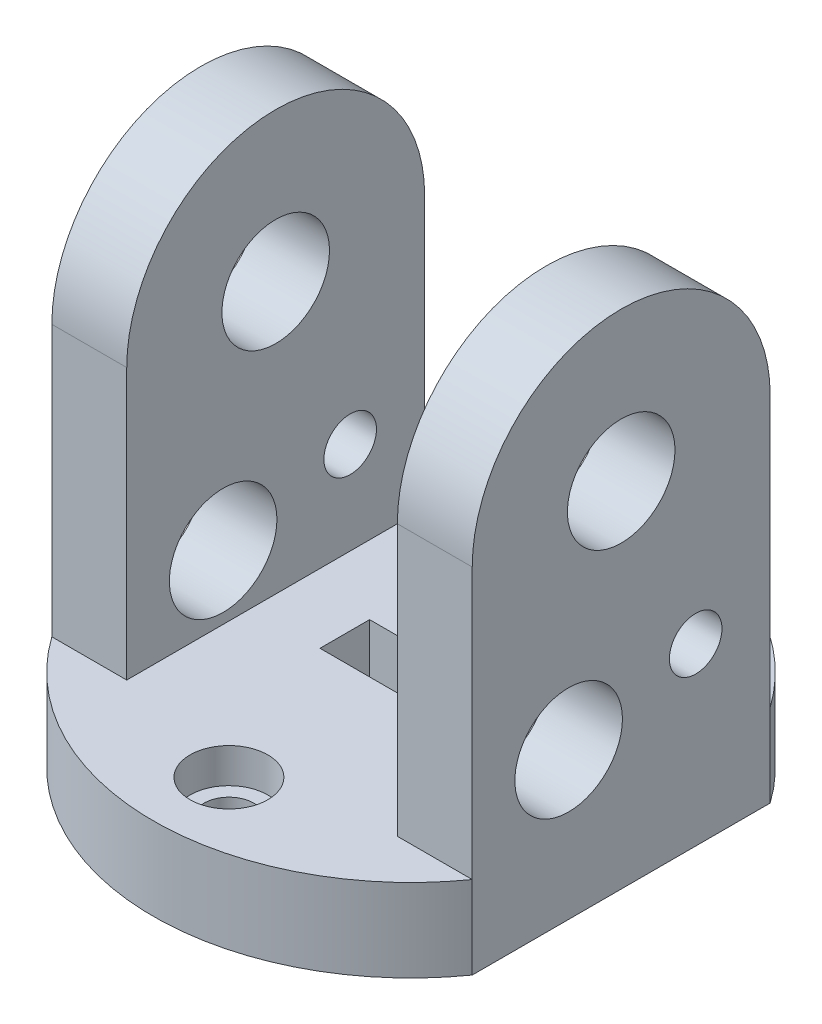
SolidWorks part; units mm, degrees
material "ABS"
ref_plane "Front Plane" through (0, 0, 0) normal (0, 0, 1) x (1, 0, 0)
ref_plane "Top Plane" through (0, 0, 0) normal (0, 1, 0) x (1, 0, 0)
ref_plane "Right Plane" through (0, 0, 0) normal (1, 0, 0) x (0, 0, -1)
sketch "Sketch1" plane through (0, 0, 0) normal (1, 0, 0) x (0, 0, -1)
  line L0 (-9, 0) -> (-9, -16.3524)
  line L1 (-9, -16.3524) -> (9, -16.3524)
  line L2 (9, -16.3524) -> (9, 0)
  line L3 (0, 0) -> (0, -16.3524) construction
  circle A0 centre (0, 0) radius 3.175
  arc A1 (-9, 0) -> (9, 0) centre (0, 0) cw
  circle A2 centre (0, 0) radius 9 construction
  circle A3 centre (-3.175, -12.4774) radius 3.175
  circle A4 centre (-3.175, -12.4774) radius 3.875 construction
  point P6 (0, -16.3524)
  dimension "D1" = 6.35
  dimension "D2" = 18
  dimension "D4" = 0.7
extrude "Main Body" add sketch "Sketch1" along normal mid plane 25.4
sketch "Sketch2" plane through (0, -16.3524, 0) normal (0, -1, 0) x (1, 0, 0)
  line L0 (-12.7, 0) -> (12.7, 0) construction
  line L1 (-12.7, 9) -> (-12.7, -9) construction
  line L2 (12.7, 9) -> (12.7, -9) construction
  circle A0 centre (0, 0) radius 17.8
  point P6 (0, 0)
  dimension "D1" = 35.6
extrude "Base Body" add sketch "Sketch2" along normal blind 3
sketch "Sketch5" plane through (0, 0, 0) normal (1, 0, 0) x (0, 0, -1)
  line L5 (-9, 0) -> (-9, -16.3524)
  line L7 (-9, -16.3524) -> (9, -16.3524)
  line L9 (9, -16.3524) -> (9, 0)
  line L10 (-9, 0) -> (-9, -16.3524)
  line L12 (-9, -16.3524) -> (9, -16.3524)
  line L14 (9, -16.3524) -> (9, 0)
  arc A1 (9, 0) -> (-9, 0) centre (0, 0) ccw
  arc A2 (9, 0) -> (-9, 0) centre (0, 0) ccw
  dimension "D1" = 0
extrude "Finger Clearance" cut sketch "Sketch5" against normal mid plane 16
sketch "Sketch3" plane through (0, -19.3524, 0) normal (0, -1, 0) x (1, 0, 0)
  line L0 (-12.7, 9) -> (-12.7, -9) construction
  line L1 (12.7, 9) -> (12.7, -9) construction
  line L2 (-12.7, 9) -> (-12.7, -9)
  line L3 (12.7, 9) -> (12.7, -9)
  arc A1 (-12.7, -9) -> (12.7, -9) centre (0, 0) ccw
  arc A2 (12.7, 9) -> (-12.7, 9) centre (0, 0) ccw
  circle A3 centre (0, 0) radius 24.9243
extrude "Outer Cut" cut sketch "Sketch3" against normal through all
sketch "Sketch7" plane through (0, -19.3524, 0) normal (0, -1, 0) x (1, 0, 0)
  line L0 (9.7, -7.9879) -> (9.7, 7.9879)
  line L1 (-9.7, 7.9879) -> (-9.7, -7.9879)
  line L2 (12.7, -9) -> (12.7, 9)
  line L3 (-12.7, 9) -> (-12.7, -9)
  line L4 (12.7, -9) -> (12.7, 9)
  line L5 (-12.7, 9) -> (-12.7, -9)
  arc A0 (-9.7, -7.9879) -> (9.7, -7.9879) centre (0, 0) ccw
  arc A1 (9.7, 7.9879) -> (-9.7, 7.9879) centre (0, 0) ccw
  arc A2 (12.7, 9) -> (-12.7, 9) centre (0, 0) ccw
  arc A3 (12.7, 9) -> (-12.7, 9) centre (0, 0) ccw
  arc A4 (-12.7, -9) -> (12.7, -9) centre (0, 0) ccw
  arc A5 (-12.7, -9) -> (12.7, -9) centre (0, 0) ccw
  arc A8 (-12.7, -9) -> (12.7, -9) centre (0, 0) ccw construction
  arc A9 (12.7, 9) -> (-12.7, 9) centre (0, 0) ccw construction
  dimension "D1" = 0
  dimension "D2" = 3
extrude "Base Flange" add sketch "Sketch7" along normal blind 2
sketch "Sketch6" plane through (0, -16.3524, 0) normal (0, 1, 0) x (1, 0, 0)
  line L0 (9.7, 0) -> (-9.7, 0) construction
  line L1 (0, -12.5657) -> (0, 12.5657) construction
  line L2 (9.7, -7.9879) -> (9.7, 7.9879)
  line L3 (-9.7, 7.9879) -> (-9.7, -7.9879)
  line L4 (9.7, -7.9879) -> (9.7, 7.9879) construction
  line L5 (-9.7, 7.9879) -> (-9.7, -7.9879) construction
  line L6 (-4, 1.5) -> (4, 1.5)
  line L7 (4, 1.5) -> (4, -1.5)
  line L8 (4, -1.5) -> (-4, -1.5)
  line L9 (-4, -1.5) -> (-4, 1.5)
  arc A3 (9.7, 7.9879) -> (-9.7, 7.9879) centre (0, 0) ccw
  arc A4 (-9.7, -7.9879) -> (9.7, -7.9879) centre (0, 0) ccw
  arc A5 (9.7, 7.9879) -> (-9.7, 7.9879) centre (0, 0) ccw construction
  arc A6 (-9.7, -7.9879) -> (9.7, -7.9879) centre (0, 0) ccw construction
  point P18 (4, 0)
  point P19 (0, 1.5)
  dimension "D1" = 8
  dimension "D5" = 3
  dimension "D2" = 0
extrude "Tendon Port" cut sketch "Sketch6" against normal through all
sketch "Sketch14" plane through (0, -19.3524, 0) normal (0, -1, 0) x (1, 0, 0)
  line L0 (0, 12.5657) -> (0, -12.5657) construction
  line L1 (-5.3333, 11.3777) -> (-5.3333, -11.3777)
  line L2 (5.3333, 11.3777) -> (5.3333, -11.3777)
  line L3 (-4, 1.5) -> (4, 1.5)
  line L4 (4, 1.5) -> (4, -1.5)
  line L5 (4, -1.5) -> (-4, -1.5)
  line L6 (-4, -1.5) -> (-4, 1.5)
  line L7 (9.7, 7.9879) -> (9.7, -7.9879) construction
  line L8 (-9.7, 7.9879) -> (-9.7, -7.9879) construction
  arc A0 (9.7, 7.9879) -> (-9.7, 7.9879) centre (0, 0) ccw construction
  arc A1 (-9.7, -7.9879) -> (9.7, -7.9879) centre (0, 0) ccw construction
  arc A2 (9.7, 7.9879) -> (-9.7, 7.9879) centre (0, 0) ccw construction
  arc A3 (-9.7, -7.9879) -> (9.7, -7.9879) centre (0, 0) ccw construction
  arc A8 (5.3333, 11.3777) -> (-5.3333, 11.3777) centre (0, 0) ccw
  arc A9 (-5.3333, -11.3777) -> (5.3333, -11.3777) centre (0, 0) ccw
  dimension "D1" = 10.6667
extrude "Central Anchor" add sketch "Sketch14" along normal up to surface (2 mm away) up to face at (0, -21.3524, 0)
sketch "Sketch9" plane through (12.7, 0, 0) normal (1, 0, 0) x (0, 0, -1)
  circle A0 centre (0, 0) radius 3.25
  circle A1 centre (-3.175, -12.4774) radius 3.25
  dimension "D1" = 6.5
extrude "Print Clearance - Base Pins" cut sketch "Sketch9" against normal through all
sketch "Sketch11" plane through (0, 0, 0) normal (1, 0, 0) x (0, 0, -1)
  line L3 (-9, 0) -> (-9, -16.3524)
  line L4 (-9, -16.3524) -> (9, -16.3524)
  line L5 (9, -16.3524) -> (9, 0)
  line L6 (-9, 0) -> (-9, -16.3524)
  line L7 (-9, -16.3524) -> (9, -16.3524)
  line L8 (9, -16.3524) -> (9, 0)
  arc A1 (9, 0) -> (-9, 0) centre (0, 0) ccw
  arc A2 (9, 0) -> (-9, 0) centre (0, 0) ccw
  dimension "D1" = 0
extrude "Print Clearance - Finger" cut sketch "Sketch11" against normal mid plane 16.35
fillet "Fit Contouring" radius 0.5 6 edges at (7.7054, -21.3524, 9.9259) (9.7, -21.3524, 0) (7.7054, -21.3524, -9.9259) (-7.7054, -21.3524, 9.9259) (-9.7, -21.3524, 0) (-7.7054, -21.3524, -9.9259)
sketch "Sketch15" plane through (12.7, 0, 0) normal (1, 0, 0) x (0, 0, -1)
  line L0 (0, -9.175) -> (26.9873, -9.175) construction
  line L1 (9, -16.3524) -> (9, 0) construction
  line L2 (9, -16.3524) -> (9, 0) construction
  line L3 (0, 0) -> (9, 0) construction
  line L4 (4.5, 0) -> (4.5, -10.7625) construction
  circle A0 centre (0, 0) radius 9.175 construction
  circle A1 centre (4.5, -10.7625) radius 1.5875
  dimension "D1" = 18.35
  dimension "D2" = 3.175
ref_point "Point1"
ref_plane "Plane1" through (0, -19.2524, 0) normal (0, -1, 0) x (-1, 0, 0)
extrude "Cut-Extrude1" cut sketch "Sketch15" against normal blind 28
sketch "Sketch20" plane through (0, -16.3524, 0) normal (0, 1, 0) x (1, 0, 0)
  line L0 (0, 15.5657) -> (0, -15.5657) construction
  line L2 (-4, 0) -> (4, 0) construction
  line L3 (-4, 1.5) -> (-4, -1.5) construction
  line L4 (4, -1.5) -> (4, 1.5) construction
  arc A0 (12.7, 9) -> (-12.7, 9) centre (0, 0) ccw construction
  arc A1 (-12.7, -9) -> (12.7, -9) centre (0, 0) ccw construction
  circle A2 centre (0, -11) radius 2.35
  circle A3 centre (0, 11) radius 2.35
  dimension "D1" = 22
  dimension "D2" = 11
  dimension "D3" = 4.7
extrude "Cut-Extrude2" cut sketch "Sketch20" against normal blind 2.1
sketch "Sketch21" plane through (0, -18.4524, 0) normal (0, 1, 0) x (1, 0, 0)
  circle A0 centre (0, 11) radius 1.5
  circle A1 centre (0, -11) radius 1.5
  dimension "D1" = 3
extrude "Cut-Extrude3" cut sketch "Sketch21" against normal up to surface (2.9 mm away) up to face at (7.879, -21.3524, 0)
